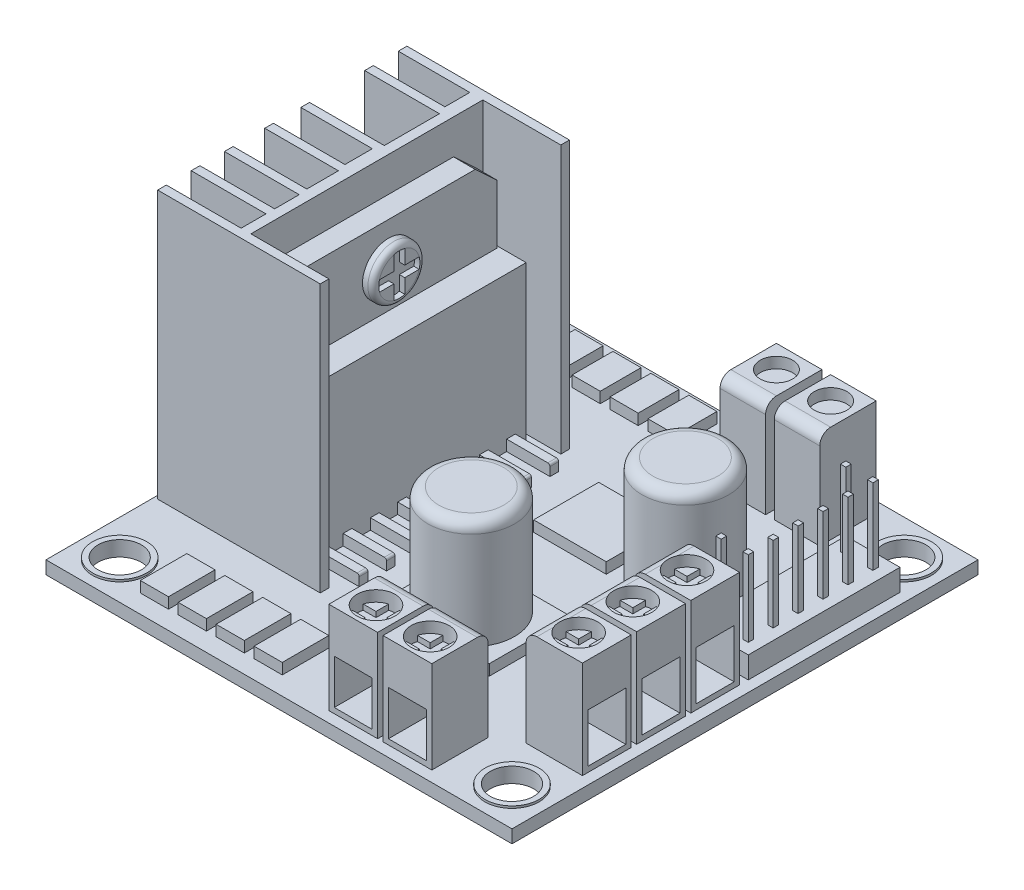
SolidWorks part; units mm, degrees
ref_plane "Alzado" through (0, 0, 0) normal (0, 0, 1) x (1, 0, 0)
ref_plane "Planta" through (0, 0, 0) normal (0, 1, 0) x (1, 0, 0)
ref_plane "Vista lateral" through (0, 0, 0) normal (1, 0, 0) x (0, 0, -1)
sketch "Croquis2" plane through (0, 0, 0) normal (0, 1, 0) x (1, 0, 0)
  line L1 (0, 0) -> (43, 0)
  line L2 (0, 0) -> (0, 43)
  line L3 (0, 43) -> (43, 43)
  line L4 (43, 0) -> (43, 43)
  dimension "D1" = 43
  dimension "D2" = 43
extrude "Saliente-Extruir1" add sketch "Croquis2" along normal blind 1.2
sketch "Croquis3" plane through (0, 1.2, 0) normal (0, 1, 0) x (1, 0, 0)
  line L0 (0, 43) -> (0, 0) construction
  line L1 (0.3042, 33) -> (15.3042, 33)
  line L2 (0.3042, 33) -> (0.3042, 10)
  line L3 (0.3042, 10) -> (15.3042, 10)
  line L4 (15.3042, 33) -> (15.3042, 10)
  point P6 (0, 21.5)
  point P7 (0.3042, 21.5)
  dimension "D1" = 23
  dimension "D2" = 15
  dimension "D3" = 0.3042
extrude "Saliente-Extruir2" add sketch "Croquis3" along normal blind 24.7
sketch "Croquis4" plane through (0, 25.9, 0) normal (0, 1, 0) x (1, 0, 0)
  line L0 (8.1042, 33) -> (8.1042, 10)
  line L1 (15.3042, 33) -> (0.3042, 33) construction
  line L2 (0.3042, 10) -> (15.3042, 10) construction
  line L3 (7.3042, 10) -> (7.3042, 33)
  line L4 (15.3042, 10) -> (15.3042, 33) construction
  line L5 (1.1042, 32.2) -> (1.1042, 10.8)
  line L6 (1.1042, 10.8) -> (14.5042, 10.8)
  line L8 (14.5042, 32.2) -> (1.1042, 32.2)
  line L9 (0.3042, 33) -> (0.3042, 10)
  line L10 (0.3042, 10) -> (15.3042, 10)
  line L11 (15.3042, 10) -> (15.3042, 33)
  line L12 (15.3042, 33) -> (0.3042, 33)
  line L13 (0.3042, 33) -> (0.3042, 10)
  line L14 (0.3042, 10) -> (15.3042, 10)
  line L15 (15.3042, 10) -> (15.3042, 33)
  line L16 (15.3042, 33) -> (0.3042, 33)
  line L17 (14.5042, 10.8) -> (15.3042, 10.8)
  line L18 (14.5042, 32.2) -> (15.3042, 32.2)
  line L21 (14.5042, 10.8) -> (14.5042, 32.2) construction
  dimension "D1" = 0.8
  dimension "D2" = 7.2
  dimension "D3" = 0
  dimension "D4" = 0.8
extrude "Cortar-Extruir2" cut sketch "Croquis4" against normal up to surface (24.7 mm away) contours L6 L21 L8 L0 | L21 L17 L15 L18 region at (11.3042, 25.9, -21.5) region at (14.9042, 25.9, -21.5) up to face at (21.5, 1.2, -21.5)
sketch "Croquis6" plane through (0, 25.9, 0) normal (0, 1, 0) x (1, 0, 0)
  line L0 (0.3042, 10.8) -> (7.2042, 10.8)
  line L1 (0.3042, 33) -> (0.3042, 10) construction
  line L2 (7.2042, 10.8) -> (7.2042, 13.0942)
  line L3 (7.2042, 13.0942) -> (0.3042, 13.0942)
  line L6 (0.3042, 10) -> (8.1042, 10)
  line L7 (0.3042, 10) -> (15.3042, 10) construction
  line L8 (8.1042, 10) -> (8.1042, 33)
  line L9 (15.3042, 33) -> (0.3042, 33) construction
  line L10 (8.1042, 33) -> (0.3042, 33)
  line L12 (0.3042, 13.0942) -> (0.3042, 10)
  line L13 (0.3042, 33) -> (0.3042, 10) construction
  line L14 (0.3042, 32.2) -> (6.9042, 32.2)
  line L15 (6.9042, 32.2) -> (6.9042, 29.9012)
  line L16 (6.9042, 29.9012) -> (0.3042, 29.9012)
  line L18 (0.3042, 29.1012) -> (7.2042, 29.1012)
  line L19 (7.2042, 29.1012) -> (7.2042, 24.0108)
  line L20 (7.2042, 24.0108) -> (0.3042, 24.0108)
  line L22 (0.3042, 23.2108) -> (6.9042, 23.2108)
  line L23 (6.9042, 23.2108) -> (6.9042, 20.6793)
  line L24 (6.9042, 20.6793) -> (0.3042, 20.6793)
  line L26 (0.3042, 19.8793) -> (7.1042, 19.8793)
  line L27 (7.1042, 19.8793) -> (7.1042, 16.9615)
  line L28 (7.1042, 16.9615) -> (0.3042, 16.9615)
  line L30 (0.3042, 16.1615) -> (7.2042, 16.1615)
  line L31 (7.2042, 16.1615) -> (7.2042, 13.8942)
  line L32 (7.2042, 13.8942) -> (0.3042, 13.8942)
  line L33 (0.3042, 33) -> (0.3042, 13.8942)
  line L34 (8.1042, 32.2) -> (8.1042, 10.8) construction
  line M31 (0.3042, 33) -> (0.3042, 10)
  dimension "D1" = 0.8
  dimension "D2" = 0.8
  dimension "D3" = 0.8
  dimension "D4" = 0.8
  dimension "D5" = 0.9
  dimension "D6" = 1
  dimension "D7" = 1.2
  dimension "D8" = 0.9
  dimension "D9" = 1.2
  dimension "D10" = 0.8
  dimension "D11" = 0.8
  dimension "D12" = 0.8
  dimension "D13" = 2.5315
  dimension "D14" = 3.0942
  dimension "D15" = 3.0673
  dimension "D16" = 3.7177
  dimension "D17" = 5.0905
extrude "Cortar-Extruir4" cut sketch "Croquis6" against normal up to surface (24.7 mm away) contours L2 L3 L0 M31 | L32 L31 L30 M31 | L28 L27 L26 M31 | L24 L23 L22 M31 | L20 L19 L18 M31 | L16 L15 L14 M31 region at (3.7542, 25.9, -11.9471) region at (3.7542, 25.9, -15.0279) region at (3.7042, 25.9, -18.4204) region at (3.6042, 25.9, -31.0506) region at (3.6042, 25.9, -21.945) region at (3.7542, 25.9, -26.556) up to face at (21.5, 1.2, -21.5)
sketch "Croquis7" plane through (8.1042, 0, 0) normal (1, 0, 0) x (0, 0, -1)
  line L0 (11.5, 15.4) -> (11.5, 20.5409)
  line L1 (11.5, 20.5409) -> (13.5, 22.7)
  line L2 (13.5, 22.7) -> (29.5, 22.7)
  line L3 (29.5, 22.7) -> (31.5, 20.8474)
  line L4 (31.5, 20.8474) -> (31.5, 15.4)
  line L5 (31.5, 15.4) -> (11.5, 15.4)
  line L6 (32.2, 25.9) -> (10.8, 25.9) construction
  line L7 (10, 25.9) -> (10, 1.2) construction
  line L8 (33, 25.9) -> (33, 1.2) construction
  point P9 (21.5, 22.7)
  point P10 (21.5, 25.9)
  dimension "D1" = 7.3
  dimension "D2" = 16
  dimension "D3" = 3.2
  dimension "D4" = 1.5
  dimension "D5" = 1.5
  dimension "D6" = 42.809
extrude "Saliente-Extruir3" add sketch "Croquis7" along normal blind 2
sketch "Croquis8" plane through (10.1042, 0, 0) normal (1, 0, 0) x (0, 0, -1)
  line L0 (11.5, 20.5409) -> (11.5, 15.4) construction
  line L1 (29.5, 22.7) -> (13.5, 22.7) construction
  line L3 (32.2, 25.9) -> (10.8, 25.9) construction
  line L4 (16.877, 21.2) -> (26.0305, 21.2) construction
  circle A0 centre (21.5, 18.8) radius 2.4
  point P11 (21.5, 25.9)
  dimension "D1" = 4.8
  dimension "D2" = 1.5
extrude "Saliente-Extruir4" add sketch "Croquis8" along normal blind 1
fillet "Redondeo1" radius 0.5 1 edges at (11.1042, 18.8, -23.9)
sketch "Croquis9" plane through (11.1042, 0, 0) normal (1, 0, 0) x (0, 0, -1)
  line L0 (21.0003, 21.1474) -> (21.0003, 19.3)
  line L1 (22.0003, 16.4527) -> (22.0003, 18.3)
  line L2 (19.1527, 19.3) -> (21.0003, 19.3)
  line L3 (19.1527, 18.3) -> (21.0003, 18.3)
  line L4 (21.0003, 18.3) -> (21.0003, 16.4526)
  line L5 (22.0003, 19.3) -> (23.8473, 19.3)
  line L6 (22.0003, 19.3) -> (22.0003, 21.1473)
  line L7 (22.0003, 18.3) -> (23.8473, 18.3)
  circle A0 centre (21.5, 18.8) radius 2.4 construction
  circle A1 centre (21.5, 18.8) radius 2.4
  circle M1 centre (21.5, 18.8) radius 1.9
  dimension "D1" = 1
  dimension "D2" = 1
  dimension "D3" = 0.5
  dimension "D4" = 0.4997
extrude "Cortar-Extruir5" cut sketch "Croquis9" against normal blind 0.5 contours L1 L7 L5 L6 L0 L2 L3 L4 M1 region at (11.1042, 18.8, -21.5001)
sketch "Croquis10" plane through (8.1042, 0, 0) normal (1, 0, 0) x (0, 0, -1)
  line L0 (32.2, 1.2) -> (10.8, 1.2) construction
  line L1 (11.3, 15.4) -> (31.7, 15.4)
  line L2 (11.3, 15.4) -> (11.3, 1.2)
  line L3 (11.3, 1.2) -> (31.7, 1.2)
  line L4 (31.7, 15.4) -> (31.7, 1.2)
  line L5 (11.5, 15.4) -> (31.5, 15.4) construction
  line L6 (10.8, 1.2) -> (10.8, 25.9) construction
  line L7 (32.2, 1.2) -> (32.2, 25.9) construction
  point P10 (10.8, 13.55)
  dimension "D1" = 0.5
  dimension "D2" = 0.5
extrude "Saliente-Extruir5" add sketch "Croquis10" along normal blind 4.5
sketch "Croquis11" plane through (12.6042, 0, 0) normal (1, 0, 0) x (0, 0, -1)
  line L0 (0, 1.2) -> (43, 1.2) construction
  line L1 (12.3, 2.2) -> (13.1, 2.2)
  line L2 (12.3, 2.2) -> (12.3, 1.2)
  line L3 (12.3, 1.2) -> (13.1, 1.2)
  line L4 (13.1, 2.2) -> (13.1, 1.2)
  line L5 (11.3, 15.4) -> (11.3, 1.2) construction
  line L6 (14.8143, 2.2) -> (14.8143, 1.2)
  line L7 (14.8143, 2.2) -> (15.6143, 2.2)
  line L8 (15.6143, 2.2) -> (15.6143, 1.2)
  line L9 (14.8143, 1.2) -> (15.6143, 1.2)
  line L10 (17.3286, 2.2) -> (17.3286, 1.2)
  line L11 (17.3286, 2.2) -> (18.1286, 2.2)
  line L12 (18.1286, 2.2) -> (18.1286, 1.2)
  line L13 (17.3286, 1.2) -> (18.1286, 1.2)
  line L14 (19.8429, 2.2) -> (19.8429, 1.2)
  line L15 (19.8429, 2.2) -> (20.6429, 2.2)
  line L16 (20.6429, 2.2) -> (20.6429, 1.2)
  line L17 (19.8429, 1.2) -> (20.6429, 1.2)
  line L18 (22.3571, 2.2) -> (22.3571, 1.2)
  line L19 (22.3571, 2.2) -> (23.1571, 2.2)
  line L20 (23.1571, 2.2) -> (23.1571, 1.2)
  line L21 (22.3571, 1.2) -> (23.1571, 1.2)
  line L22 (24.8714, 2.2) -> (24.8714, 1.2)
  line L23 (24.8714, 2.2) -> (25.6714, 2.2)
  line L24 (25.6714, 2.2) -> (25.6714, 1.2)
  line L25 (24.8714, 1.2) -> (25.6714, 1.2)
  line L26 (27.3857, 2.2) -> (27.3857, 1.2)
  line L27 (27.3857, 2.2) -> (28.1857, 2.2)
  line L28 (28.1857, 2.2) -> (28.1857, 1.2)
  line L29 (27.3857, 1.2) -> (28.1857, 1.2)
  line L30 (29.9, 2.2) -> (29.9, 1.2)
  line L31 (29.9, 2.2) -> (30.7, 2.2)
  line L32 (30.7, 2.2) -> (30.7, 1.2)
  line L33 (29.9, 1.2) -> (30.7, 1.2)
  line L34 (31.7, 1.2) -> (31.7, 15.4) construction
  dimension "D1" = 0.8
  dimension "D2" = 1
  dimension "D3" = 1
  dimension "D5" = 1
  dimension "D4" = 8
extrude "Saliente-Extruir6" add sketch "Croquis11" along normal blind 4
fillet "Redondeo3" radius 0.2 8 edges at (16.6042, 2.2, -30.3) (16.6042, 2.2, -27.7857) (16.6042, 2.2, -25.2714) (16.6042, 2.2, -22.7571) (16.6042, 2.2, -20.2429) (16.6042, 2.2, -17.7286) (16.6042, 2.2, -15.2143) (16.6042, 2.2, -12.7)
sketch "Croquis13" plane through (0, 1.2, 0) normal (0, 1, 0) x (1, 0, 0)
  line L0 (19.7524, 18.6917) -> (19.7524, 11.1917)
  line L1 (19.7524, 11.1917) -> (20.9441, 10)
  line L2 (20.9441, 10) -> (28.5607, 10)
  line L3 (28.5607, 10) -> (29.7524, 11.1917)
  line L4 (29.7524, 11.1917) -> (29.7524, 18.6917)
  line L5 (29.7524, 18.6917) -> (19.7524, 18.6917)
  line L6 (0.3042, 10) -> (15.3042, 10) construction
  line L7 (16.6042, 19.8429) -> (12.6042, 19.8429) construction
  line L8 (16.6042, 14.8143) -> (16.6042, 15.6143) construction
  point P12 (16.6042, 15.2143)
  dimension "D1" = 10
  dimension "D2" = 7.5
  dimension "D3" = 1.1512
  dimension "D4" = 3.1482
  dimension "D5" = 1.6853
extrude "Saliente-Extruir8" add sketch "Croquis13" along normal blind 1
sketch "Croquis14" plane through (0, 2.2, 0) normal (0, 1, 0) x (1, 0, 0)
  line L0 (19.7524, 18.6917) -> (19.7524, 11.1917) construction
  line L1 (29.7524, 18.6917) -> (19.7524, 18.6917) construction
  line L2 (29.7524, 18.6917) -> (19.7524, 18.6917) construction
  circle A0 centre (24.7524, 14.4917) radius 4
  point P11 (24.7524, 18.6917)
  dimension "D1" = 8
  dimension "D2" = 4.2
extrude "Saliente-Extruir9" add sketch "Croquis14" along normal blind 10
fillet "Redondeo4" radius 1 1 edges at (24.7524, 12.2, -10.4917)
sketch "Croquis15" plane through (0, 1.2, 0) normal (0, 1, 0) x (1, 0, 0)
  line L0 (0, 43) -> (0, 0) construction
  line L1 (43, 43) -> (0, 43) construction
  line L2 (43, 0) -> (43, 43) construction
  line L3 (0, 0) -> (43, 0) construction
  circle A0 centre (3.4, 3.4) radius 2
  circle A1 centre (39.6, 3.4) radius 2
  circle A2 centre (39.6, 39.6) radius 2
  circle A3 centre (3.4, 39.6) radius 2
  circle A4 centre (39.6, 39.6) radius 2.5
  circle A5 centre (3.4, 39.6) radius 2.5
  circle A6 centre (39.6, 3.4) radius 2.5
  circle A7 centre (3.4, 3.4) radius 2.5
  dimension "D1" = 4
  dimension "D2" = 3.4
  dimension "D3" = 3.4
  dimension "D4" = 3.4
  dimension "D5" = 3.4
  dimension "D6" = 3.4
  dimension "D7" = 3.4
  dimension "D8" = 3.4
  dimension "D9" = 3.4
  dimension "D10" = 0.5
extrude "Saliente-Extruir10" add sketch "Croquis15" along normal blind 0.2
sketch "Croquis16" plane through (0, 1.2, 0) normal (0, 1, 0) x (1, 0, 0)
  circle A0 centre (3.4, 39.6) radius 2 construction
  circle A1 centre (39.6, 3.4) radius 2 construction
  circle A2 centre (3.4, 3.4) radius 2 construction
  circle A3 centre (3.4, 39.6) radius 2
  circle A4 centre (39.6, 3.4) radius 2
  circle A5 centre (3.4, 3.4) radius 2
  circle A6 centre (39.6, 39.6) radius 2 construction
  circle A7 centre (39.6, 39.6) radius 2
extrude "Cortar-Extruir6" cut sketch "Croquis16" against normal through all
sketch "Croquis17" plane through (0, 1.2, 0) normal (0, 1, 0) x (1, 0, 0)
  line L0 (29.7524, 18.6917) -> (19.7524, 18.6917) construction
  line L1 (20.3042, 30.6917) -> (27.0042, 30.6917)
  line L2 (20.3042, 30.6917) -> (20.3042, 24.6917)
  line L3 (20.3042, 24.6917) -> (27.0042, 24.6917)
  line L4 (27.0042, 30.6917) -> (27.0042, 24.6917)
  dimension "D1" = 6.7
  dimension "D2" = 6
  dimension "D3" = 5
  dimension "D4" = 6
extrude "Saliente-Extruir11" add sketch "Croquis17" along normal blind 1
sketch "Croquis18" plane through (0, 1.2, 0) normal (0, 1, 0) x (1, 0, 0)
  line L0 (0, 0) -> (43, 0) construction
  line L1 (7, 6) -> (9.6, 6)
  line L2 (7, 6) -> (7, 1.7)
  line L3 (7, 1.7) -> (9.6, 1.7)
  line L4 (9.6, 6) -> (9.6, 1.7)
  line L5 (0, 43) -> (0, 0) construction
  line L6 (10.5, 6) -> (10.5, 1.7)
  line L7 (10.5, 6) -> (13.1, 6)
  line L8 (13.1, 6) -> (13.1, 1.7)
  line L9 (10.5, 1.7) -> (13.1, 1.7)
  line L10 (14, 6) -> (14, 1.7)
  line L11 (14, 6) -> (16.6, 6)
  line L12 (16.6, 6) -> (16.6, 1.7)
  line L13 (14, 1.7) -> (16.6, 1.7)
  line L14 (17.5, 6) -> (17.5, 1.7)
  line L15 (17.5, 6) -> (20.1, 6)
  line L16 (20.1, 6) -> (20.1, 1.7)
  line L17 (17.5, 1.7) -> (20.1, 1.7)
  line L18 (43, 0) -> (43, 43) construction
  dimension "D1" = 2.6
  dimension "D2" = 4.3
  dimension "D3" = 1.7
  dimension "D4" = 7
  dimension "D6" = 22.9
  dimension "D5" = 4
extrude "Saliente-Extruir12" add sketch "Croquis18" along normal blind 1
sketch "Croquis19" plane through (0, 1.2, 0) normal (0, 1, 0) x (1, 0, 0)
  line L0 (0, 0) -> (43, 0) construction
  line L1 (25.1, 6.2) -> (29.6, 6.2)
  line L2 (25.1, 6.2) -> (25.1, 1)
  line L3 (25.1, 1) -> (29.6, 1)
  line L4 (29.6, 6.2) -> (29.6, 1)
  line L5 (20.1, 1.7) -> (20.1, 6) construction
  line L6 (30.1, 6.2) -> (30.1, 1)
  line L7 (30.1, 6.2) -> (34.6, 6.2)
  line L8 (34.6, 6.2) -> (34.6, 1)
  line L9 (30.1, 1) -> (34.6, 1)
  line L10 (43, 0) -> (43, 43) construction
  dimension "D1" = 5.2
  dimension "D2" = 4.5
  dimension "D3" = 1
  dimension "D4" = 5
  dimension "D6" = 8.4
  dimension "D5" = 2
extrude "Saliente-Extruir13" add sketch "Croquis19" along normal blind 8.5
fillet "Redondeo5" radius 1 2 edges at (27.35, 9.7, -6.2) (32.35, 9.7, -6.2)
sketch "Croquis20" plane through (0, 0, -1) normal (0, 0, 1) x (1, 0, 0)
  line L0 (25.1, 1.2) -> (29.6, 1.2) construction
  line L1 (25.6, 5.8) -> (29.1, 5.8)
  line L2 (25.6, 5.8) -> (25.6, 1.7)
  line L3 (25.6, 1.7) -> (29.1, 1.7)
  line L4 (29.1, 5.8) -> (29.1, 1.7)
  line L5 (25.1, 9.7) -> (25.1, 1.2) construction
  line L6 (29.6, 9.7) -> (29.6, 1.2) construction
  line L7 (25.1, 9.7) -> (29.6, 9.7) construction
  line L8 (30.6, 5.8) -> (30.6, 1.7)
  line L9 (30.6, 5.8) -> (34.1, 5.8)
  line L10 (34.1, 5.8) -> (34.1, 1.7)
  line L11 (30.6, 1.7) -> (34.1, 1.7)
  line L12 (34.6, 9.7) -> (34.6, 1.2) construction
  dimension "D1" = 0.5
  dimension "D2" = 0.5
  dimension "D3" = 0.5
  dimension "D4" = 3.9
  dimension "D6" = 0.5
  dimension "D5" = 2
extrude "Cortar-Extruir7" cut sketch "Croquis20" against normal offset from surface (4.2 mm away) 1 up to face at (32.35, 4.95, -6.2)
sketch "Croquis21" plane through (0, 9.7, 0) normal (0, 1, 0) x (1, 0, 0)
  line L0 (25.1, 5.2) -> (25.1, 1) construction
  line L1 (25.1, 1) -> (29.6, 1) construction
  line L2 (30.1, 1) -> (34.6, 1) construction
  circle A0 centre (27.35, 3.1) radius 1.75
  circle A1 centre (32.35, 3.1) radius 1.75
  point P4 (25.1, 3.1)
  point P7 (27.35, 1)
  point P12 (32.35, 1)
  dimension "D1" = 3.5
extrude "Cortar-Extruir8" cut sketch "Croquis21" against normal blind 1
sketch "Croquis22" plane through (0, 8.7, 0) normal (0, 1, 0) x (1, 0, 0)
  line L0 (26.85, 4.7771) -> (26.85, 3.6)
  line L1 (27.85, 1.4229) -> (27.85, 2.6)
  line L2 (25.6729, 3.6) -> (26.85, 3.6)
  line L3 (25.6729, 2.6) -> (26.85, 2.6)
  line L4 (27.85, 3.6) -> (29.0271, 3.6)
  line L5 (26.85, 2.6) -> (26.85, 1.4229)
  line L6 (27.85, 2.6) -> (29.0271, 2.6)
  line L7 (27.85, 3.6) -> (27.85, 4.7771)
  line L8 (30.6729, 2.6) -> (31.85, 2.6)
  line L9 (31.85, 2.6) -> (31.85, 1.4229)
  line L10 (32.85, 1.4229) -> (32.85, 2.6)
  line L11 (32.85, 2.6) -> (34.0271, 2.6)
  line L12 (32.85, 3.6) -> (34.0271, 3.6)
  line L13 (32.85, 3.6) -> (32.85, 4.7771)
  line L14 (31.85, 4.7771) -> (31.85, 3.6)
  line L15 (30.6729, 3.6) -> (31.85, 3.6)
  circle A0 centre (27.35, 3.1) radius 1.75 construction
  circle A1 centre (27.35, 3.1) radius 1.75 construction
  circle A2 centre (27.35, 3.1) radius 1.75
  circle A3 centre (32.35, 3.1) radius 1.75 construction
  circle A4 centre (32.35, 3.1) radius 1.75
  circle M8 centre (27.35, 3.1) radius 1.75
  dimension "D1" = 0.5
  dimension "D2" = 0.5
  dimension "D3" = 0.5
  dimension "D4" = 0.5
extrude "Cortar-Extruir9" cut sketch "Croquis22" against normal blind 0.5 contours L4 L7 L0 L2 L3 L5 L1 L6 M8 | L11 A4 L12 L13 L14 L15 L8 L9 L10 region at (27.35, 8.7, -3.1) region at (32.35, 8.7, -3.1)
sketch "Croquis23" plane through (0, 1.2, 0) normal (0, 1, 0) x (1, 0, 0)
  line L0 (27.0042, 24.6917) -> (27.0042, 30.6917) construction
  line L1 (43, 0) -> (43, 43) construction
  circle A0 centre (31.3116, 27.6917) radius 4
  circle A1 centre (24.7524, 14.4917) radius 4 construction
  point P7 (27.0042, 27.6917)
  dimension "D1" = 11.6884
extrude "Saliente-Extruir14" add sketch "Croquis23" along normal blind 10
fillet "Redondeo6" radius 1 1 edges at (31.3116, 11.2, -23.6917)
sketch "Croquis24" plane through (0, 1.2, 0) normal (0, 1, 0) x (1, 0, 0)
  line L0 (0, 0) -> (43, 0) construction
  line L1 (36.8, 12) -> (42, 12)
  line L2 (36.8, 12) -> (36.8, 7.5)
  line L3 (36.8, 7.5) -> (42, 7.5)
  line L4 (42, 12) -> (42, 7.5)
  line L5 (43, 0) -> (43, 43) construction
  line L6 (36.8, 17) -> (36.8, 12.5)
  line L7 (36.8, 17) -> (42, 17)
  line L8 (42, 17) -> (42, 12.5)
  line L9 (36.8, 12.5) -> (42, 12.5)
  line L10 (36.8, 22) -> (36.8, 17.5)
  line L11 (36.8, 22) -> (42, 22)
  line L12 (42, 22) -> (42, 17.5)
  line L13 (36.8, 17.5) -> (42, 17.5)
  line L14 (43, 43) -> (0, 43) construction
  dimension "D1" = 4.5
  dimension "D2" = 5.2
  dimension "D3" = 7.5
  dimension "D4" = 1
  dimension "D6" = 21
  dimension "D5" = 3
extrude "Saliente-Extruir15" add sketch "Croquis24" along normal blind 9
sketch "Croquis25" plane through (42, 0, 0) normal (1, 0, 0) x (0, 0, -1)
  line L0 (7.5, 1.2) -> (12, 1.2) construction
  line L1 (8, 6.2) -> (11.5, 6.2)
  line L2 (8, 6.2) -> (8, 1.7)
  line L3 (8, 1.7) -> (11.5, 1.7)
  line L4 (11.5, 6.2) -> (11.5, 1.7)
  line L5 (7.5, 10.2) -> (7.5, 1.2) construction
  line L6 (12, 10.2) -> (12, 1.2) construction
  line L7 (7.5, 10.2) -> (12, 10.2) construction
  line L8 (13, 6.2) -> (13, 1.7)
  line L9 (13, 6.2) -> (16.5, 6.2)
  line L10 (16.5, 6.2) -> (16.5, 1.7)
  line L11 (13, 1.7) -> (16.5, 1.7)
  line L12 (18, 6.2) -> (18, 1.7)
  line L13 (18, 6.2) -> (21.5, 6.2)
  line L14 (21.5, 6.2) -> (21.5, 1.7)
  line L15 (18, 1.7) -> (21.5, 1.7)
  line L16 (22, 10.2) -> (22, 1.2) construction
  dimension "D1" = 0.5
  dimension "D2" = 0.5
  dimension "D3" = 0.5
  dimension "D4" = 4
  dimension "D6" = 0.5
  dimension "D5" = 3
extrude "Cortar-Extruir10" cut sketch "Croquis25" against normal offset from surface (4.2 mm away) 1 up to face at (36.8, 5.7, -9.75)
sketch "Croquis26" plane through (0, 10.2, 0) normal (0, 1, 0) x (1, 0, 0)
  line L0 (36.8, 7.5) -> (42, 7.5) construction
  line L1 (42, 7.5) -> (42, 12) construction
  line L2 (42, 22) -> (36.8, 22) construction
  circle A0 centre (39.4, 9.75) radius 1.75
  circle A1 centre (39.4, 14.75) radius 1.75
  circle A2 centre (39.4, 19.75) radius 1.75
  point P4 (39.4, 7.5)
  point P7 (42, 9.75)
  dimension "D1" = 3.5
  dimension "D2" = 2.25
extrude "Cortar-Extruir11" cut sketch "Croquis26" against normal blind 1
sketch "Croquis27" plane through (0, 9.2, 0) normal (0, 1, 0) x (1, 0, 0)
  line L0 (38.9, 11.4271) -> (38.9, 10.25)
  line L1 (39.9, 8.0729) -> (39.9, 9.25)
  line L2 (37.7229, 10.25) -> (38.9, 10.25)
  line L3 (37.7229, 9.25) -> (38.9, 9.25)
  line L4 (39.9, 10.25) -> (41.0771, 10.25)
  line L5 (38.9, 9.25) -> (38.9, 8.0729)
  line L6 (39.9, 10.25) -> (39.9, 11.4271)
  line L7 (39.9, 9.25) -> (41.0771, 9.25)
  line L8 (38.9, 16.4271) -> (38.9, 15.25)
  line L9 (37.7229, 15.25) -> (38.9, 15.25)
  line L10 (37.7229, 14.25) -> (38.9, 14.25)
  line L11 (38.9, 14.25) -> (38.9, 13.0729)
  line L12 (39.9, 13.0729) -> (39.9, 14.25)
  line L13 (39.9, 14.25) -> (41.0771, 14.25)
  line L14 (39.9, 15.25) -> (41.0771, 15.25)
  line L15 (39.9, 15.25) -> (39.9, 16.4271)
  line L16 (38.9, 21.4271) -> (38.9, 20.25)
  line L17 (37.7229, 20.25) -> (38.9, 20.25)
  line L18 (37.7229, 19.25) -> (38.9, 19.25)
  line L19 (38.9, 19.25) -> (38.9, 18.0729)
  line L20 (39.9, 18.0729) -> (39.9, 19.25)
  line L21 (39.9, 19.25) -> (41.0771, 19.25)
  line L22 (39.9, 20.25) -> (41.0771, 20.25)
  line L23 (39.9, 20.25) -> (39.9, 21.4271)
  circle A0 centre (39.4, 9.75) radius 1.75 construction
  circle A1 centre (39.4, 9.75) radius 1.75 construction
  circle A2 centre (39.4, 9.75) radius 1.75
  circle A3 centre (39.4, 19.75) radius 1.75 construction
  circle A4 centre (39.4, 14.75) radius 1.75 construction
  circle A5 centre (39.4, 19.75) radius 1.75
  circle A6 centre (39.4, 14.75) radius 1.75
  circle M7 centre (39.4, 9.75) radius 1.75
  dimension "D1" = 0.5
  dimension "D2" = 0.5
  dimension "D3" = 0.5
  dimension "D4" = 0.5
  dimension "D5" = 3
extrude "Cortar-Extruir12" cut sketch "Croquis27" against normal blind 0.5 contours L21 A5 L22 L23 L16 L17 L18 L19 L20 | L13 A6 L14 L15 L8 L9 L10 L11 L12 | L1 L7 L4 L6 L0 L2 L3 L5 M7 region at (39.4, 9.2, -9.75) region at (39.4, 9.2, -14.75) region at (39.4, 9.2, -19.75)
sketch "Croquis28" plane through (0, 1.2, 0) normal (0, 1, 0) x (1, 0, 0)
  line L0 (42, 22) -> (36.8, 22) construction
  line L1 (37, 22.8) -> (42, 22.8)
  line L2 (37, 22.8) -> (37, 36.8)
  line L3 (37, 36.8) -> (42, 36.8)
  line L4 (42, 22.8) -> (42, 36.8)
  line L5 (43, 0) -> (43, 43) construction
  dimension "D1" = 14
  dimension "D2" = 0.8
  dimension "D3" = 5
  dimension "D4" = 1
extrude "Saliente-Extruir16" add sketch "Croquis28" along normal blind 2
sketch "Croquis29" plane through (0, 3.2, 0) normal (0, 1, 0) x (1, 0, 0)
  line L0 (42, 22.8) -> (42, 36.8) construction
  line L1 (40.5, 24.3) -> (41, 24.3)
  line L2 (40.5, 24.3) -> (40.5, 23.8)
  line L3 (40.5, 23.8) -> (41, 23.8)
  line L4 (41, 24.3) -> (41, 23.8)
  line L5 (37, 22.8) -> (42, 22.8) construction
  line L6 (40.5, 26.6) -> (40.5, 26.1)
  line L7 (40.5, 26.6) -> (41, 26.6)
  line L8 (41, 26.6) -> (41, 26.1)
  line L9 (40.5, 26.1) -> (41, 26.1)
  line L10 (40.5, 28.9) -> (40.5, 28.4)
  line L11 (40.5, 28.9) -> (41, 28.9)
  line L12 (41, 28.9) -> (41, 28.4)
  line L13 (40.5, 28.4) -> (41, 28.4)
  line L14 (40.5, 31.2) -> (40.5, 30.7)
  line L15 (40.5, 31.2) -> (41, 31.2)
  line L16 (41, 31.2) -> (41, 30.7)
  line L17 (40.5, 30.7) -> (41, 30.7)
  line L18 (40.5, 33.5) -> (40.5, 33)
  line L19 (40.5, 33.5) -> (41, 33.5)
  line L20 (41, 33.5) -> (41, 33)
  line L21 (40.5, 33) -> (41, 33)
  line L22 (40.5, 35.8) -> (40.5, 35.3)
  line L23 (40.5, 35.8) -> (41, 35.8)
  line L24 (41, 35.8) -> (41, 35.3)
  line L25 (40.5, 35.3) -> (41, 35.3)
  line L26 (42, 36.8) -> (37, 36.8) construction
  dimension "D1" = 0.5
  dimension "D2" = 0.5
  dimension "D3" = 1
  dimension "D4" = 1
  dimension "D5" = 1
extrude "Saliente-Extruir17" add sketch "Croquis29" along normal blind 7
sketch "Croquis30" plane through (0, 3.2, 0) normal (0, 1, 0) x (1, 0, 0)
  line L0 (41, 24.3) -> (40.5, 24.3) construction
  line L1 (38, 35.8) -> (38.5, 35.8)
  line L2 (38, 35.8) -> (38, 35.3)
  line L3 (38, 35.3) -> (38.5, 35.3)
  line L4 (38.5, 35.8) -> (38.5, 35.3)
  line L5 (38.0043, 24.3) -> (38.5043, 24.3)
  line L6 (38.0043, 24.3) -> (38.0043, 23.8)
  line L7 (38.0043, 23.8) -> (38.5043, 23.8)
  line L8 (38.5043, 24.3) -> (38.5043, 23.8)
  line L9 (40.5, 24.3) -> (40.5, 23.8) construction
  line L10 (40.5, 35.8) -> (40.5, 35.3) construction
  line L11 (41, 35.8) -> (40.5, 35.8) construction
  dimension "D1" = 0.5
  dimension "D2" = 0.5
  dimension "D3" = 1.9957
  dimension "D4" = 2
  dimension "D5" = 0.5
  dimension "D6" = 0.5
extrude "Saliente-Extruir18" add sketch "Croquis30" along normal blind 7
sketch "Croquis31" plane through (0, 1.2, 0) normal (0, 1, 0) x (1, 0, 0)
  line L1 (30.4, 42) -> (34.6, 42)
  line L2 (30.4, 42) -> (30.4, 36.8)
  line L3 (30.4, 36.8) -> (34.6, 36.8)
  line L4 (34.6, 42) -> (34.6, 36.8)
  line L5 (25.4, 42) -> (29.6, 42)
  line L6 (25.4, 42) -> (25.4, 36.8)
  line L7 (25.4, 36.8) -> (29.6, 36.8)
  line L8 (29.6, 42) -> (29.6, 36.8)
  line L9 (34.6, 1) -> (34.6, 5.2) construction
  line L10 (29.6, 1) -> (29.6, 6.2) construction
  line L11 (43, 43) -> (0, 43) construction
  dimension "D1" = 1
  dimension "D2" = 5.2
  dimension "D3" = 5.2
  dimension "D4" = 4.2
  dimension "D5" = 4.2
extrude "Saliente-Extruir19" add sketch "Croquis31" along normal blind 9
fillet "Redondeo7" radius 1 2 edges at (32.5, 10.2, -36.8) (27.5, 10.2, -36.8)
fillet "Redondeo8" radius 1 3 edges at (36.8, 10.2, -9.75) (36.8, 10.2, -14.75) (36.8, 10.2, -19.75)
sketch "Croquis32" plane through (0, 0, -42) normal (0, 0, -1) x (-1, 0, 0)
  line L0 (-43, 1.2) -> (0, 1.2) construction
  line L1 (-34.1, 6.2) -> (-30.9, 6.2)
  line L2 (-34.1, 6.2) -> (-34.1, 1.7)
  line L3 (-34.1, 1.7) -> (-30.9, 1.7)
  line L4 (-30.9, 6.2) -> (-30.9, 1.7)
  line L5 (-34.6, 10.2) -> (-34.6, 1.2) construction
  line L6 (-30.4, 10.2) -> (-30.4, 1.2) construction
  line L7 (-34.6, 10.2) -> (-30.4, 10.2) construction
  line L8 (-29.1, 6.2) -> (-29.1, 1.7)
  line L9 (-29.1, 6.2) -> (-25.9, 6.2)
  line L10 (-25.9, 6.2) -> (-25.9, 1.7)
  line L11 (-29.1, 1.7) -> (-25.9, 1.7)
  line L12 (-25.4, 10.2) -> (-25.4, 1.2) construction
  dimension "D1" = 0.5
  dimension "D2" = 0.5
  dimension "D3" = 0.5
  dimension "D4" = 4
  dimension "D6" = 0.5
  dimension "D5" = 2
extrude "Cortar-Extruir13" cut sketch "Croquis32" against normal offset from surface (4.2 mm away) 1 up to face at (32.5, 5.2, -36.8)
sketch "Croquis33" plane through (0, 10.2, 0) normal (0, 1, 0) x (1, 0, 0)
  line L0 (30.4, 37.8) -> (34.6, 37.8) construction
  line L1 (34.6, 37.8) -> (34.6, 42) construction
  line L2 (25.4, 42) -> (25.4, 36.8) construction
  circle A0 centre (32.5, 39.9) radius 1.5
  circle A1 centre (27.5, 39.9) radius 1.5
  point P4 (32.5, 37.8)
  point P7 (34.6, 39.9)
  dimension "D1" = 3
  dimension "D2" = 2.1
extrude "Cortar-Extruir14" cut sketch "Croquis33" against normal blind 1
sketch "Croquis34" plane through (0, 1.2, 0) normal (0, 1, 0) x (1, 0, 0)
  line L0 (7, 6) -> (7, 1.7) construction
  line L1 (7, 41.8112) -> (9.6, 41.8112)
  line L2 (7, 41.8112) -> (7, 38.0421)
  line L3 (7, 38.0421) -> (9.6, 38.0421)
  line L4 (9.6, 41.8112) -> (9.6, 38.0421)
  line L5 (9.6, 1.7) -> (9.6, 6) construction
  line L6 (43, 43) -> (0, 43) construction
  line L7 (15.3042, 33) -> (0.3042, 33) construction
  line L8 (10.5, 41.8112) -> (10.5, 38.0421)
  line L9 (10.5, 41.8112) -> (13.1, 41.8112)
  line L10 (13.1, 41.8112) -> (13.1, 38.0421)
  line L11 (10.5, 38.0421) -> (13.1, 38.0421)
  line L12 (14, 41.8112) -> (14, 38.0421)
  line L13 (14, 41.8112) -> (16.6, 41.8112)
  line L14 (16.6, 41.8112) -> (16.6, 38.0421)
  line L15 (14, 38.0421) -> (16.6, 38.0421)
  line L16 (17.5, 41.8112) -> (17.5, 38.0421)
  line L17 (17.5, 41.8112) -> (20.1, 41.8112)
  line L18 (20.1, 41.8112) -> (20.1, 38.0421)
  line L19 (17.5, 38.0421) -> (20.1, 38.0421)
  line L20 (20.1, 1.7) -> (20.1, 6) construction
  point P12 (7.8042, 33)
  dimension "D1" = 1.1888
  dimension "D2" = 5.0421
  dimension "D3" = 4
extrude "Saliente-Extruir20" add sketch "Croquis34" along normal blind 1
